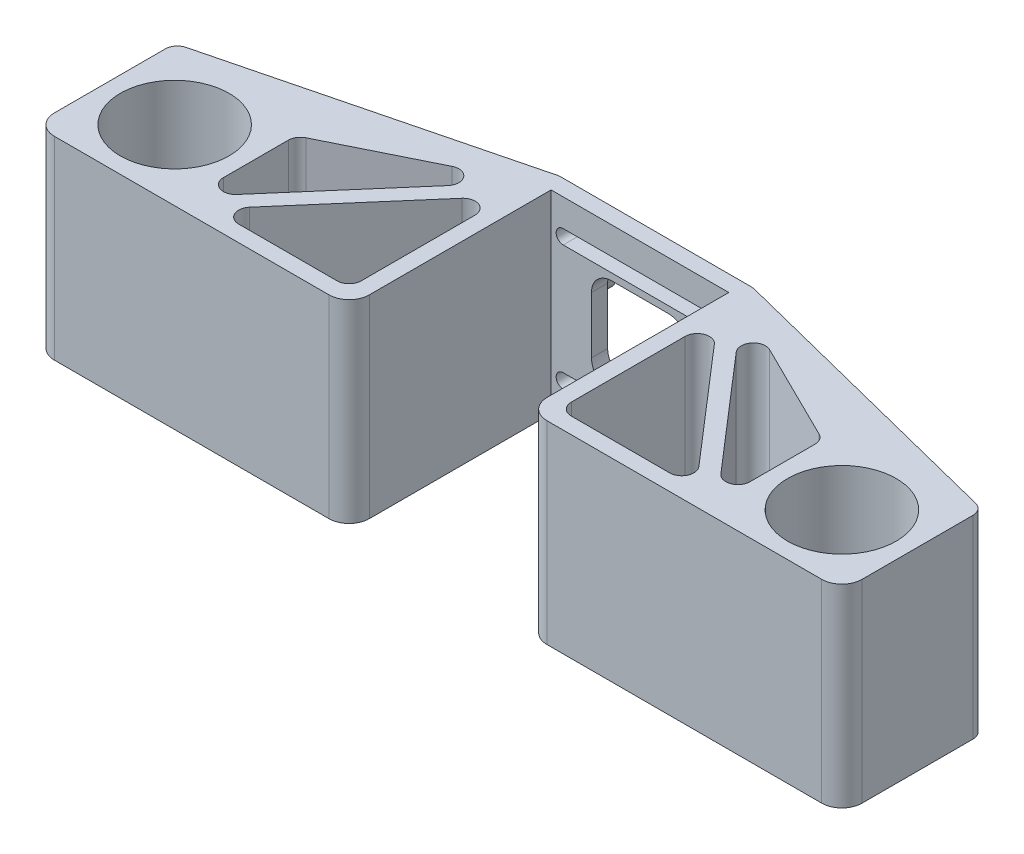
SolidWorks part; units mm, degrees
ref_plane "Front Plane" through (0, 0, 0) normal (0, 0, 1) x (1, 0, 0)
ref_plane "Top Plane" through (0, 0, 0) normal (0, 1, 0) x (1, 0, 0)
ref_plane "Right Plane" through (0, 0, 0) normal (1, 0, 0) x (0, 0, -1)
sketch "Sketch2" plane through (0, 0, 0) normal (0, 1, 0) x (1, 0, 0)
  line L0 (-17.4, -17.4) -> (82.6, -17.4) construction
  line L1 (-17.4, -17.4) -> (17.4, -17.4)
  line L2 (-17.4, -17.4) -> (-17.4, 17.4)
  line L5 (0, 17.4) -> (0, -17.4) construction
  line L6 (-17.4, 0) -> (17.4, 12.6) construction
  line L7 (82.6, -17.4) -> (82.6, 36.6) construction
  line L8 (17.4, -13.4) -> (17.4, 12.6)
  line L9 (82.6, 36.6) -> (58.6, 36.6)
  line L10 (82.6, 36.6) -> (82.6, 32.6)
  line L11 (82.6, 32.6) -> (60.6, 32.6)
  line L13 (17.4, 12.6) -> (56.6, 31.9691)
  line L14 (58.6, 36.6) -> (-17.4, 17.4)
  line L20 (56.6, -13.4) -> (56.6, 25.8509)
  line L22 (56.6, 31.9691) -> (17.4, -13.4)
  line L23 (22.6863, -13.4) -> (56.6, 25.8509)
  line L24 (56.6, -13.4) -> (22.6863, -13.4)
  line L25 (60.6, 32.6) -> (60.6, -17.4)
  line L26 (60.6, -17.4) -> (17.4, -17.4)
  circle A0 centre (0, 0) radius 13.45
  point P0 (0, 0)
  point P13 (0, 0)
  point P17 (24.4098, -13.4907)
  point P18 (0, 0)
  point P19 (0, 0)
  point P20 (0, 0)
  point P21 (0, 0)
  point P22 (17.4, 10.1063)
  point P23 (17.4, 9.62)
  point P24 (17.4, 17.4)
  point P25 (17.4, 11.079)
  point P26 (17.4, 14.0798)
  point P27 (56.6, 32.6)
  point P28 (17.4, -13.4)
  point P29 (0, 0)
  point P30 (0, 0)
  dimension "D3" = 26.9
  dimension "D8" = 17.4
  dimension "D9" = 17.4
  dimension "D10" = 4
  dimension "D15" = 26
  dimension "D1" = 34.8
  dimension "D2" = 34.8
  dimension "D4" = 100
  dimension "D5" = 54
  dimension "D6" = 24
  dimension "D7" = 4
  dimension "D11" = 22
  dimension "D12" = 4
  dimension "D13" = 4
  dimension "D14" = 4
extrude "Boss-Extrude1" add sketch "Sketch2" along normal blind 48
sketch3d "3DSketch1"
  line L0 (82.6, 0, -36.6) -> (82.6, 0, -32.6) construction
  line L1 (82.6, 0, -32.6) -> (82.6, 48, -32.6) construction
ref_plane "Plane1" through (82.6, 0, 0) normal (1, 0, 0) x (0, 0, -1)
mirror "Mirror1" about plane through (82.6, 0, 0) normal (1, 0, 0) of "Boss-Extrude1"
sketch "Sketch4" plane through (0, 0, -36.6) normal (0, 0, -1) x (-1, 0, 0)
  line L0 (-106.6, 24) -> (-58.6, 24) construction
  line L1 (-58.6, 48) -> (-58.6, 0) construction
  line L2 (-101.6, 8.55) -> (-63.6, 8.55) construction
  line L3 (-101.6, 10.3) -> (-63.6, 10.3)
  line L4 (-82.6, 0) -> (-82.6, 48) construction
  line L5 (-101.6, 6.8) -> (-63.6, 6.8)
  line L6 (-101.6, 39.45) -> (-63.6, 39.45) construction
  line L7 (-101.6, 37.7) -> (-63.6, 37.7)
  line L8 (-101.6, 41.2) -> (-63.6, 41.2)
  line L10 (-89.6, 12) -> (-75.6, 12)
  line L11 (-94.6, 17) -> (-94.6, 31)
  line L12 (-89.6, 36) -> (-75.6, 36)
  line L13 (-70.6, 17) -> (-70.6, 31)
  line L14 (-94.6, 12) -> (-70.6, 36) construction
  line L15 (-94.6, 36) -> (-70.6, 12) construction
  arc A0 (-101.6, 10.3) -> (-101.6, 6.8) centre (-101.6, 8.55) ccw
  arc A1 (-63.6, 6.8) -> (-63.6, 10.3) centre (-63.6, 8.55) ccw
  arc A2 (-101.6, 37.7) -> (-101.6, 41.2) centre (-101.6, 39.45) cw
  arc A3 (-63.6, 41.2) -> (-63.6, 37.7) centre (-63.6, 39.45) cw
  arc A5 (-94.6, 17) -> (-89.6, 12) centre (-89.6, 17) ccw
  arc A6 (-75.6, 12) -> (-70.6, 17) centre (-75.6, 17) ccw
  arc A7 (-70.6, 31) -> (-75.6, 36) centre (-75.6, 31) ccw
  arc A8 (-94.6, 31) -> (-89.6, 36) centre (-89.6, 31) cw
  circle A9 centre (-82.6, 24) radius 12 construction
  point P5 (-82.6, 24)
  point P7 (-82.6, 8.55)
  point P10 (-82.6, 24)
  point P17 (-82.6, 39.45)
  dimension "D4" = 24
  dimension "D6" = 5
  dimension "D1" = 15.45
  dimension "D2" = 1.75
  dimension "D3" = 38
  dimension "D5" = 24
extrude "Cut-Extrude1" cut sketch "Sketch4" against normal blind 10
ref_plane "Plane2" through (0, 0, -36.6) normal (0, 0, -1) x (-1, 0, 0)
sketch "Sketch5" plane through (0, 0, -36.6) normal (0, 0, -1) x (-1, 0, 0)
  line L0 (-107.3963, 24) -> (-21.5979, 24) construction
  line L1 (-82.6, 2.2) -> (-82.6, -2.2) construction
  line L2 (-106.6, 24) -> (-58.6, 24) construction
  line L3 (-59.6, 31) -> (-45.6, 31)
  line L4 (-59.6, 31) -> (-59.6, 17)
  line L5 (-59.6, 17) -> (-45.6, 17)
  line L6 (-45.6, 31) -> (-45.6, 17)
  line L7 (-59.6, 31) -> (-45.6, 17) construction
  line L8 (-59.6, 17) -> (-45.6, 31) construction
  circle A0 centre (-52.6, 24) radius 4.1
  dimension "D1" = 8.2
  dimension "D2" = 30
  dimension "D3" = 14
  dimension "D4" = 14
extrude "Boss-Extrude2" add sketch "Sketch5" along normal blind 13 and the other way through all
sketch "Sketch6" plane through (0, 0, -49.6) normal (0, 0, -1) x (-1, 0, 0)
  circle A0 centre (-52.6, 24) radius 4.1 construction
  circle A1 centre (-52.6, 24) radius 4.1
extrude "Cut-Extrude2" cut sketch "Sketch6" against normal up to vertex (63 mm away) up to point (45.6, 31, 13.4)
fillet "Fillet1" radius 5 4 edges at (182.6, 24, 17.4) (104.6, 24, 17.4) (60.6, 24, 17.4) (-17.4, 24, 17.4)
fillet "Fillet2" radius 3 14 edges at (108.6, 24, -31.9691) (108.6, 24, -25.8509) (108.6, 24, 13.4) (142.5137, 24, 13.4) (147.8, 24, 13.4) (147.8, 24, -12.6) (22.6863, 24, 13.4) (17.4, 24, -12.6) (17.4, 24, 13.4) (182.6, 24, -17.4) (106.6, 24, -36.6) (58.6, 8.5, -36.6) (58.6, 39.5, -36.6) (-17.4, 24, -17.4)
fillet "Fillet3" radius 3 13 edges at (45.6, 31, 0.1401) (56.6, 31, -6.2254) (45.6, 17, 0.1401) (56.6, 17, -6.2254) (56.6, 8.5, -25.8509) (56.6, 39.5, -25.8509) (56.6, 8.5, 13.4) (56.6, 39.5, 13.4) (56.6, 39.5, -31.9691) (45.6, 17, -41.4579) (59.6, 17, -43.1) (59.6, 31, -43.1) (45.6, 31, -41.4579)
